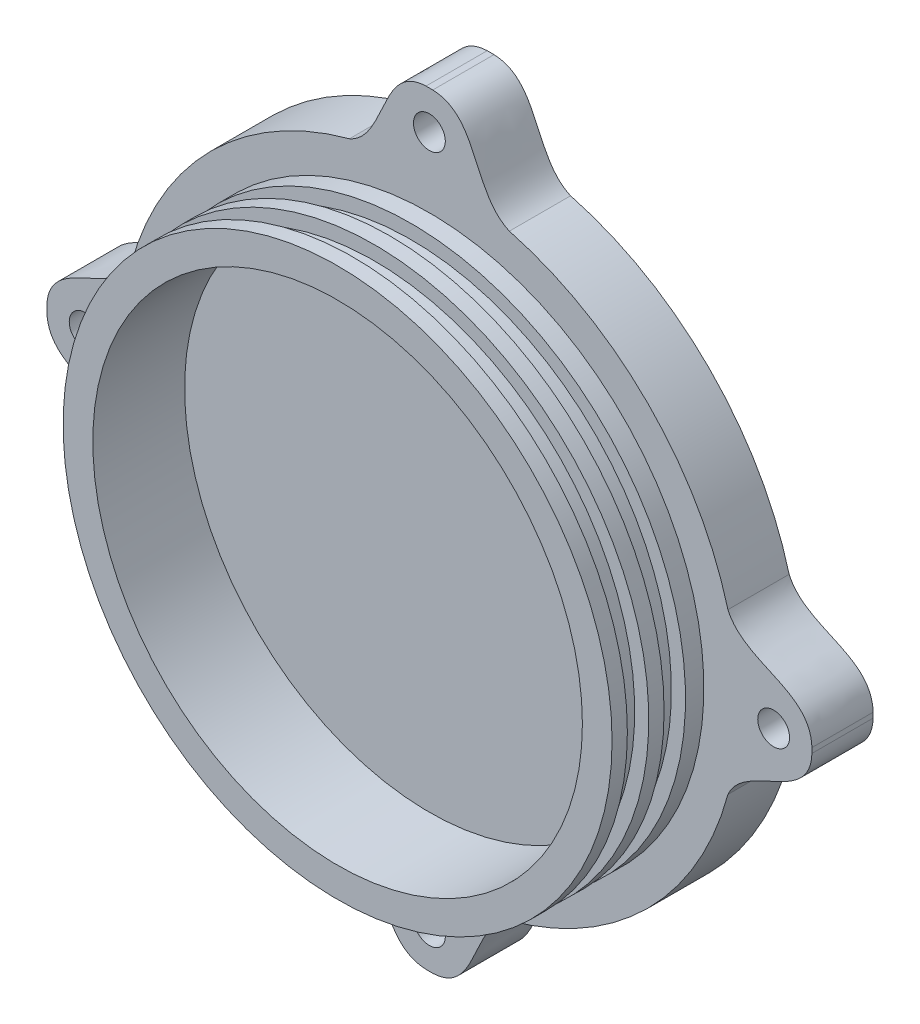
SolidWorks part; units mm, degrees
material "6063-T6"
ref_plane "Front Plane" through (0, 0, 0) normal (0, 0, 1) x (1, 0, 0)
ref_plane "Top Plane" through (0, 0, 0) normal (0, 1, 0) x (1, 0, 0)
ref_plane "Right Plane" through (0, 0, 0) normal (1, 0, 0) x (0, 0, -1)
sketch "Sketch1" plane through (0, 0, 0) normal (0, 0, 1) x (1, 0, 0)
  circle A0 centre (0, 0) radius 44.85
  circle A1 centre (0, 0) radius 45.15 construction
  dimension "D1" = 89.7
  dimension "D2" = 90.3
  dimension "D3" = 0.3
extrude "Boss-Extrude1" add sketch "Sketch1" along normal blind 15
sketch "Sketch2" plane through (0, 0, 0) normal (0, 0, -1) x (-1, 0, 0)
  circle A0 centre (0, 0) radius 62.5
  circle A1 centre (0, 0) radius 50 construction
  dimension "D1" = 125
  dimension "D2" = 100
extrude "Boss-Extrude2" add sketch "Sketch2" along normal blind 10
sketch "Sketch3" plane through (0, 0, 15) normal (0, 0, 1) x (1, 0, 0)
  circle A0 centre (0, 0) radius 40
  dimension "D1" = 80
extrude "Cut-Extrude1" cut sketch "Sketch3" against normal blind 15
sketch "Sketch4" plane through (0, 0, 0) normal (1, 0, 0) x (0, 0, -1)
  line L0 (42.7131, 0) -> (-42.7131, 0) construction
  line L1 (-48.7015, 45.15) -> (43.3244, 45.15) construction
  line L2 (-15, 44.85) -> (-15, -44.85) construction
  line L3 (0, 62.5) -> (0, -62.5) construction
  line L4 (-7.5, 59.1563) -> (-7.5, -7.7145) construction
  line L6 (-12.5, 46.05) -> (-9, 46.05)
  line L7 (-12.5, 46.05) -> (-12.5, 42.55)
  line L8 (-12.5, 42.55) -> (-9, 42.55)
  line L9 (-9, 46.05) -> (-9, 42.55)
  line L18 (-6.5, 46.05) -> (-3, 46.05)
  line L19 (-6.5, 46.05) -> (-6.5, 42.55)
  line L20 (-6.5, 42.55) -> (-3, 42.55)
  line L21 (-3, 46.05) -> (-3, 42.55)
  point P5 (0, 0)
  dimension "D5" = 3.5
  dimension "D6" = 2.6
  dimension "D1" = 45.15
  dimension "D2" = 15
  dimension "D3" = 7.5
  dimension "D4" = 3.5
  dimension "D7" = 2.6
  dimension "D8" = 2.5
  dimension "D9" = 3
  dimension "D10" = 2.5
revolve "Cut-Revolve1" cut sketch "Sketch4" angle 360 about L0
sketch "Sketch5" plane through (0, 0, 0) normal (0, 0, 1) x (1, 0, 0)
  circle A0 centre (0, 0) radius 44.9 construction
  circle A1 centre (0, 0) radius 50 construction
  circle A2 centre (0, 0) radius 46
  circle A3 centre (0, 0) radius 48.8
  dimension "D1" = 89.8
  dimension "D2" = 100
  dimension "D3" = 97.6
  dimension "D4" = 92
  dimension "D5" = 2.8
extrude "Cut-Extrude2" [suppressed] cut sketch "Sketch5" against normal blind 1.5
sketch "Sketch7" plane through (0, 0, -10) normal (0, 0, -1) x (-1, 0, 0)
  line L0 (0, 0) -> (81.7368, 0) construction
  line L1 (50, -30.8838) -> (50, 30.8838) construction
  circle A0 centre (0, 0) radius 44.75 construction
  circle A1 centre (0, 0) radius 50 construction
  circle A3 centre (0, 0) radius 62.5 construction
  circle A4 centre (56.25, 0) radius 2.6
  circle A5 centre (56.25, 0) radius 5 construction
  point P12 (50, 0)
  dimension "D1" = 89.5
  dimension "D2" = 100
  dimension "D3" = 125
  dimension "D4" = 5.2
  dimension "D5" = 10
  dimension "D6" = 6.25
extrude "Cut-Extrude4" cut sketch "Sketch7" against normal through all
ref_axis "Axis1" through (0, 0, -45.8748) along (0, 0, 1)
pattern_circular "CirPattern1" count 4 over 360 about axis through (0, 0, -45.8748) along (0, 0, 1) of "Cut-Extrude4"
sketch "Sketch8" plane through (0, 0, 0) normal (0, 0, 1) x (1, 0, 0)
  line L0 (0, 0) -> (68.0582, 0) construction
  circle A0 centre (36.25, 0) radius 1.6
  circle A1 centre (0, 0) radius 36.25 construction
  dimension "D1" = 3.2
  dimension "D2" = 72.5
extrude "Cut-Extrude5" [suppressed] cut sketch "Sketch8" against normal blind 5
pattern_circular "CirPattern2" [suppressed] count 4 over 360 about axis through (0, 0, -45.8748) along (0, 0, 1) of bodies 129
sketch "Sketch9" plane through (0, 0, 0) normal (0, 0, 1) x (1, 0, 0)
  line L0 (0, 0) -> (68.6501, 0) construction
  line L1 (56.25, 0) -> (56.25, 7.5) construction
  line L2 (56.25, 0) -> (60.714, 4.7247) construction
  line L3 (0, 0) -> (48.7793, 13.0704) construction
  circle A1 centre (0, 0) radius 50.5
  circle A2 centre (0, 0) radius 62.5 construction
  circle A3 centre (0, 0) radius 62.5
  spline S0 degree 3 poles (62.5, 0) (62.6669, 8.1946) (51.5, 6.8618) (48.7793, 13.0704) knots 0 0 0 0 1 1 1 1
  spline S1 degree 3 poles (62.5, 0) (62.6669, -8.1946) (51.5, -6.8618) (48.7793, -13.0704) knots 0 0 0 0 1 1 1 1
  spline S2 degree 3 poles (0, -62.5) (8.1554, -62.7289) (6.8897, -51.4602) (13.0704, -48.7793) knots 0 0 0 0 1 1 1 1
  spline S3 degree 3 poles (0, -62.5) (-8.1554, -62.7289) (-6.8897, -51.4602) (-13.0704, -48.7793) knots 0 0 0 0 1 1 1 1
  spline S4 degree 3 poles (-62.5, 0) (-62.7289, -8.1554) (-51.4602, -6.8897) (-48.7793, -13.0704) knots 0 0 0 0 1 1 1 1
  spline S5 degree 3 poles (-62.5, 0) (-62.7289, 8.1554) (-51.4602, 6.8897) (-48.7793, 13.0704) knots 0 0 0 0 1 1 1 1
  spline S6 degree 3 poles (0, 62.5) (-8.1554, 62.7289) (-6.8897, 51.4602) (-13.0704, 48.7793) knots 0 0 0 0 1 1 1 1
  spline S7 degree 3 poles (0, 62.5) (8.1554, 62.7289) (6.8897, 51.4602) (13.0704, 48.7793) knots 0 0 0 0 1 1 1 1
  point P43 (0, 0)
  dimension "D4" = 101
  dimension "D1" = 6.5
  dimension "D2" = 7.5
  dimension "D3" = 15
extrude "Cut-Extrude6" cut sketch "Sketch9" against normal blind 10 contours S4 A3 S3 A1 | S6 A3 S5 A1 | S2 A3 S1 A1 | A3 S7 A1 S0 region at (37.4269, 37.4237, 0) region at (37.4269, -37.4237, 0) region at (-37.4256, 37.4256, 0) region at (-37.4256, -37.4256, 0)
sketch "Sketch10" plane through (0, 0, 0) normal (0, 0, 1) x (1, 0, 0)
  line L1 (15, 15) -> (-15, 15) construction
  line L2 (-15, 15) -> (-15, -15) construction
  line L3 (-15, -15) -> (15, -15) construction
  line L4 (15, -15) -> (15, 15) construction
  circle A0 centre (0, 0) radius 15 construction
  circle A1 centre (-15, 15) radius 5.1
  circle A2 centre (-15, -15) radius 5.1
  circle A3 centre (15, 15) radius 5.5
  circle A4 centre (0, 0) radius 5.5
  circle A5 centre (15, -15) radius 5.5
  dimension "D1" = 10.2
  dimension "D2" = 10.2
  dimension "D3" = 11
  dimension "D4" = 11
  dimension "D5" = 11
  dimension "D6" = 30
extrude "Cut-Extrude7" [suppressed] cut sketch "Sketch10" against normal blind 10
